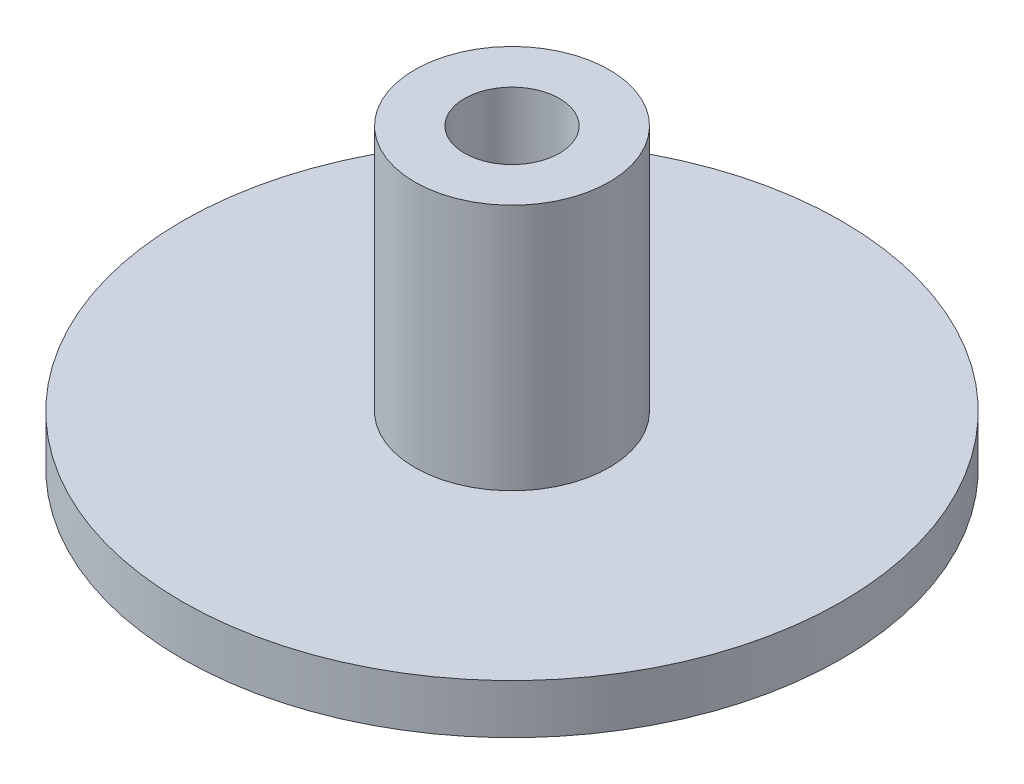
SolidWorks part; units mm, degrees
ref_plane "Plan de face" through (0, 0, 0) normal (0, 0, 1) x (1, 0, 0)
ref_plane "Plan de dessus" through (0, 0, 0) normal (0, 1, 0) x (1, 0, 0)
ref_plane "Plan de droite" through (0, 0, 0) normal (1, 0, 0) x (0, 0, -1)
sketch "Esquisse1" plane through (0, 0, 0) normal (0, 1, 0) x (1, 0, 0)
  circle A0 centre (0, 0) radius 10
  circle A1 centre (0, 0) radius 2.95
  circle A2 centre (0, 0) radius 1.44
  dimension "D1" = 20
  dimension "D2" = 5.9
extrude "Boss.-Extru.2" add sketch "Esquisse1" along normal blind 1.5 contours A0 A1 region at (-9.7172, 0, 0)
extrude "Boss.-Extru.3" add sketch "Esquisse1<5>" along normal blind 9 contours A1 A2 region at (-2.8666, 0, 0)
sketch "Esquisse1<5>" plane through (0, 0, 0) normal (0, 1, 0) x (1, 0, 0) same geometry as "Esquisse1"
